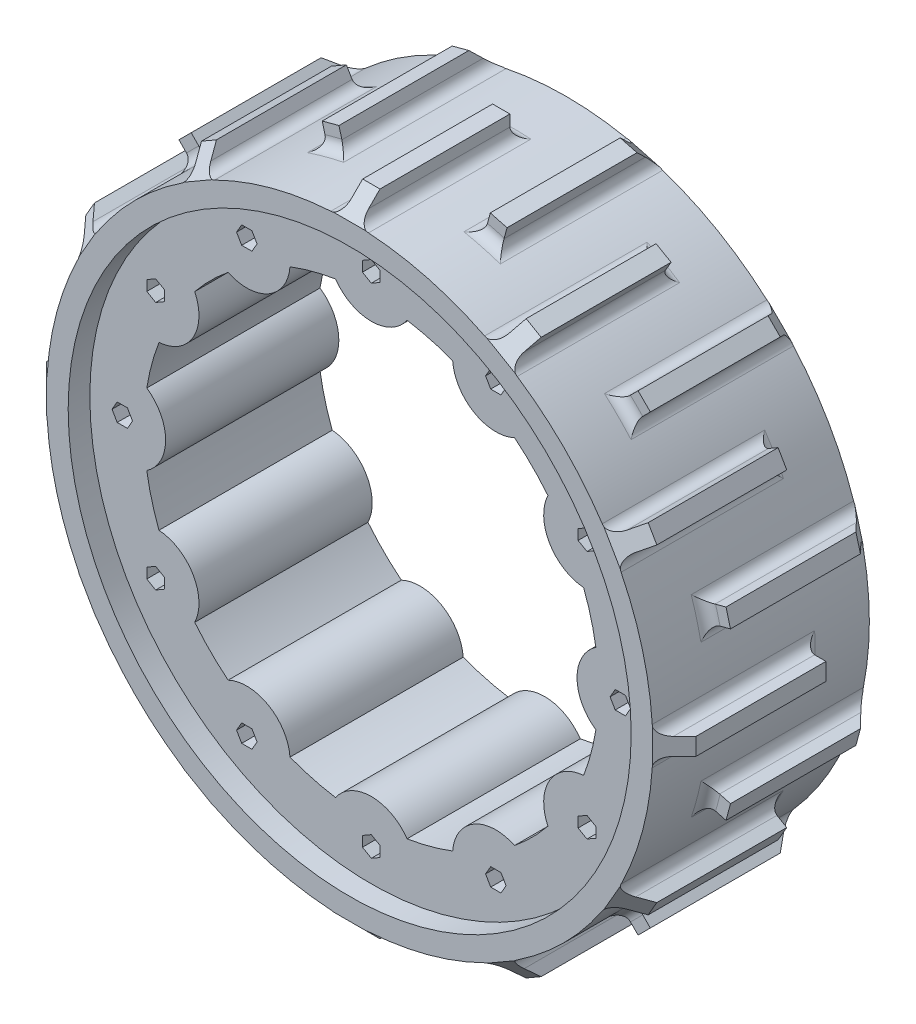
SolidWorks part; units mm, degrees
material "ABS"
ref_plane "前视基准面" through (0, 0, 0) normal (0, 0, 1) x (1, 0, 0)
ref_plane "上视基准面" through (0, 0, 0) normal (0, 1, 0) x (1, 0, 0)
ref_plane "右视基准面" through (0, 0, 0) normal (1, 0, 0) x (0, 0, -1)
other "Configuration Table"
sketch "草图1" plane through (0, 0, 0) normal (0, 0, 1) x (1, 0, 0)
  circle A0 centre (0, 0) radius 140
  dimension "D1" = 280
extrude "凸台-拉伸1" add sketch "草图1" along normal blind 100
sketch "草图2" plane through (0, 0, 100) normal (0, 0, 1) x (1, 0, 0)
  circle A0 centre (0, 0) radius 105
  dimension "D1" = 210
extrude "切除-拉伸1" cut sketch "草图2" against normal blind 100
sketch "草图3" plane through (0, 0, 100) normal (0, 0, 1) x (1, 0, 0)
  circle A0 centre (0, 0) radius 115 construction
  circle A1 centre (0, 115) radius 20
  circle A2 centre (57.5, 99.5929) radius 20
  circle A3 centre (99.5929, 57.5) radius 20
  circle A4 centre (115, 0) radius 20
  circle A5 centre (99.5929, -57.5) radius 20
  circle A6 centre (57.5, -99.5929) radius 20
  circle A7 centre (0, -115) radius 20
  circle A8 centre (-57.5, -99.5929) radius 20
  circle A9 centre (-99.5929, -57.5) radius 20
  circle A10 centre (-115, 0) radius 20
  circle A11 centre (-99.5929, 57.5) radius 20
  circle A12 centre (-57.5, 99.5929) radius 20
  point P30 (0, 0)
  dimension "D1" = 230
  dimension "D2" = 40
  dimension "D3" = 12
extrude "凸台-拉伸2" add sketch "草图3" against normal through all
sketch "草图4" plane through (0, 0, 100) normal (0, 0, 1) x (1, 0, 0)
  circle A0 centre (0, 0) radius 130
  dimension "D1" = 260
extrude "切除-拉伸2" cut sketch "草图4" against normal blind 10
sketch "草图5" plane through (0, 0, 0) normal (0, 0, -1) x (-1, 0, 0)
  circle A1 centre (0, 0) radius 130
  circle A2 centre (0, 0) radius 130
  dimension "D1" = 0
extrude "切除-拉伸3" cut sketch "草图5" against normal blind 10
sketch "草图6" plane through (0, 0, 90) normal (0, 0, 1) x (1, 0, 0)
  line L0 (55.1329, 95.4929) -> (59.8671, 95.4929)
  line L1 (0, 110.2657) -> (4.1, 112.6329)
  line L2 (4.1, 112.6329) -> (4.1, 117.3671)
  line L3 (4.1, 117.3671) -> (0, 119.7343)
  line L4 (0, 119.7343) -> (-4.1, 117.3671)
  line L5 (-4.1, 117.3671) -> (-4.1, 112.6329)
  line L6 (-4.1, 112.6329) -> (0, 110.2657)
  line L7 (59.8671, 95.4929) -> (62.2343, 99.5929)
  line L8 (62.2343, 99.5929) -> (59.8671, 103.6929)
  line L9 (59.8671, 103.6929) -> (55.1329, 103.6929)
  line L10 (55.1329, 103.6929) -> (52.7657, 99.5929)
  line L11 (52.7657, 99.5929) -> (55.1329, 95.4929)
  line L12 (95.4929, 55.1329) -> (99.5929, 52.7657)
  line L13 (99.5929, 52.7657) -> (103.6929, 55.1329)
  line L14 (103.6929, 55.1329) -> (103.6929, 59.8671)
  line L15 (103.6929, 59.8671) -> (99.5929, 62.2343)
  line L16 (99.5929, 62.2343) -> (95.4929, 59.8671)
  line L17 (95.4929, 59.8671) -> (95.4929, 55.1329)
  line L18 (110.2657, 0) -> (112.6329, -4.1)
  line L19 (112.6329, -4.1) -> (117.3671, -4.1)
  line L20 (117.3671, -4.1) -> (119.7343, 0)
  line L21 (119.7343, 0) -> (117.3671, 4.1)
  line L22 (117.3671, 4.1) -> (112.6329, 4.1)
  line L23 (112.6329, 4.1) -> (110.2657, 0)
  line L24 (95.4929, -55.1329) -> (95.4929, -59.8671)
  line L25 (95.4929, -59.8671) -> (99.5929, -62.2343)
  line L26 (99.5929, -62.2343) -> (103.6929, -59.8671)
  line L27 (103.6929, -59.8671) -> (103.6929, -55.1329)
  line L28 (103.6929, -55.1329) -> (99.5929, -52.7657)
  line L29 (99.5929, -52.7657) -> (95.4929, -55.1329)
  line L30 (55.1329, -95.4929) -> (52.7657, -99.5929)
  line L31 (52.7657, -99.5929) -> (55.1329, -103.6929)
  line L32 (55.1329, -103.6929) -> (59.8671, -103.6929)
  line L33 (59.8671, -103.6929) -> (62.2343, -99.5929)
  line L34 (62.2343, -99.5929) -> (59.8671, -95.4929)
  line L35 (59.8671, -95.4929) -> (55.1329, -95.4929)
  line L36 (0, -110.2657) -> (-4.1, -112.6329)
  line L37 (-4.1, -112.6329) -> (-4.1, -117.3671)
  line L38 (-4.1, -117.3671) -> (0, -119.7343)
  line L39 (0, -119.7343) -> (4.1, -117.3671)
  line L40 (4.1, -117.3671) -> (4.1, -112.6329)
  line L41 (4.1, -112.6329) -> (0, -110.2657)
  line L42 (-55.1329, -95.4929) -> (-59.8671, -95.4929)
  line L43 (-59.8671, -95.4929) -> (-62.2343, -99.5929)
  line L44 (-62.2343, -99.5929) -> (-59.8671, -103.6929)
  line L45 (-59.8671, -103.6929) -> (-55.1329, -103.6929)
  line L46 (-55.1329, -103.6929) -> (-52.7657, -99.5929)
  line L47 (-52.7657, -99.5929) -> (-55.1329, -95.4929)
  line L48 (-95.4929, -55.1329) -> (-99.5929, -52.7657)
  line L49 (-99.5929, -52.7657) -> (-103.6929, -55.1329)
  line L50 (-103.6929, -55.1329) -> (-103.6929, -59.8671)
  line L51 (-103.6929, -59.8671) -> (-99.5929, -62.2343)
  line L52 (-99.5929, -62.2343) -> (-95.4929, -59.8671)
  line L53 (-95.4929, -59.8671) -> (-95.4929, -55.1329)
  line L54 (-110.2657, 0) -> (-112.6329, 4.1)
  line L55 (-112.6329, 4.1) -> (-117.3671, 4.1)
  line L56 (-117.3671, 4.1) -> (-119.7343, 0)
  line L57 (-119.7343, 0) -> (-117.3671, -4.1)
  line L58 (-117.3671, -4.1) -> (-112.6329, -4.1)
  line L59 (-112.6329, -4.1) -> (-110.2657, 0)
  line L60 (-95.4929, 55.1329) -> (-95.4929, 59.8671)
  line L61 (-95.4929, 59.8671) -> (-99.5929, 62.2343)
  line L62 (-99.5929, 62.2343) -> (-103.6929, 59.8671)
  line L63 (-103.6929, 59.8671) -> (-103.6929, 55.1329)
  line L64 (-103.6929, 55.1329) -> (-99.5929, 52.7657)
  line L65 (-99.5929, 52.7657) -> (-95.4929, 55.1329)
  line L66 (-55.1329, 95.4929) -> (-52.7657, 99.5929)
  line L67 (-52.7657, 99.5929) -> (-55.1329, 103.6929)
  line L68 (-55.1329, 103.6929) -> (-59.8671, 103.6929)
  line L69 (-59.8671, 103.6929) -> (-62.2343, 99.5929)
  line L70 (-62.2343, 99.5929) -> (-59.8671, 95.4929)
  line L71 (-59.8671, 95.4929) -> (-55.1329, 95.4929)
  circle A0 centre (0, 115) radius 4.1 construction
  circle A1 centre (57.5, 99.5929) radius 4.1 construction
  circle A2 centre (99.5929, 57.5) radius 4.1 construction
  circle A3 centre (115, 0) radius 4.1 construction
  circle A4 centre (99.5929, -57.5) radius 4.1 construction
  circle A5 centre (57.5, -99.5929) radius 4.1 construction
  circle A6 centre (0, -115) radius 4.1 construction
  circle A7 centre (-57.5, -99.5929) radius 4.1 construction
  circle A8 centre (-99.5929, -57.5) radius 4.1 construction
  circle A9 centre (-115, 0) radius 4.1 construction
  circle A10 centre (-99.5929, 57.5) radius 4.1 construction
  circle A11 centre (-57.5, 99.5929) radius 4.1 construction
  point P100 (0, 0)
  dimension "D1" = 8.2
  dimension "D2" = 12
extrude "切除-拉伸4" cut sketch "草图6" against normal through all
sketch "草图7" plane through (0, 0, 100) normal (0, 0, 1) x (1, 0, 0)
  line L0 (0, 0) -> (0, 139.9428) construction
  line L1 (66.5073, 123.1941) -> (73.4355, 119.1941)
  line L2 (-4, 139.9428) -> (4, 139.9428)
  line L3 (-4, 139.9428) -> (-4, 149.9428)
  line L4 (-4, 149.9428) -> (4, 149.9428)
  line L5 (4, 139.9428) -> (4, 149.9428)
  line L6 (73.4355, 119.1941) -> (78.4355, 127.8543)
  line L7 (66.5073, 123.1941) -> (71.5073, 131.8543)
  line L8 (71.5073, 131.8543) -> (78.4355, 127.8543)
  line L9 (119.1941, 73.4355) -> (123.1941, 66.5073)
  line L10 (123.1941, 66.5073) -> (131.8543, 71.5073)
  line L11 (119.1941, 73.4355) -> (127.8543, 78.4355)
  line L12 (127.8543, 78.4355) -> (131.8543, 71.5073)
  line L13 (139.9428, 4) -> (139.9428, -4)
  line L14 (139.9428, -4) -> (149.9428, -4)
  line L15 (139.9428, 4) -> (149.9428, 4)
  line L16 (149.9428, 4) -> (149.9428, -4)
  line L17 (123.1941, -66.5073) -> (119.1941, -73.4355)
  line L18 (119.1941, -73.4355) -> (127.8543, -78.4355)
  line L19 (123.1941, -66.5073) -> (131.8543, -71.5073)
  line L20 (131.8543, -71.5073) -> (127.8543, -78.4355)
  line L21 (73.4355, -119.1941) -> (66.5073, -123.1941)
  line L22 (66.5073, -123.1941) -> (71.5073, -131.8543)
  line L23 (73.4355, -119.1941) -> (78.4355, -127.8543)
  line L24 (78.4355, -127.8543) -> (71.5073, -131.8543)
  line L25 (4, -139.9428) -> (-4, -139.9428)
  line L26 (-4, -139.9428) -> (-4, -149.9428)
  line L27 (4, -139.9428) -> (4, -149.9428)
  line L28 (4, -149.9428) -> (-4, -149.9428)
  line L29 (-66.5073, -123.1941) -> (-73.4355, -119.1941)
  line L30 (-73.4355, -119.1941) -> (-78.4355, -127.8543)
  line L31 (-66.5073, -123.1941) -> (-71.5073, -131.8543)
  line L32 (-71.5073, -131.8543) -> (-78.4355, -127.8543)
  line L33 (-119.1941, -73.4355) -> (-123.1941, -66.5073)
  line L34 (-123.1941, -66.5073) -> (-131.8543, -71.5073)
  line L35 (-119.1941, -73.4355) -> (-127.8543, -78.4355)
  line L36 (-127.8543, -78.4355) -> (-131.8543, -71.5073)
  line L37 (-139.9428, -4) -> (-139.9428, 4)
  line L38 (-139.9428, 4) -> (-149.9428, 4)
  line L39 (-139.9428, -4) -> (-149.9428, -4)
  line L40 (-149.9428, -4) -> (-149.9428, 4)
  line L41 (-123.1941, 66.5073) -> (-119.1941, 73.4355)
  line L42 (-119.1941, 73.4355) -> (-127.8543, 78.4355)
  line L43 (-123.1941, 66.5073) -> (-131.8543, 71.5073)
  line L44 (-131.8543, 71.5073) -> (-127.8543, 78.4355)
  line L45 (-73.4355, 119.1941) -> (-66.5073, 123.1941)
  line L46 (-66.5073, 123.1941) -> (-71.5073, 131.8543)
  line L47 (-73.4355, 119.1941) -> (-78.4355, 127.8543)
  line L48 (-78.4355, 127.8543) -> (-71.5073, 131.8543)
  circle A1 centre (0, 0) radius 140 construction
  point P57 (0, 0)
  dimension "D1" = 10
  dimension "D2" = 8
  dimension "D3" = 12
extrude "凸台-拉伸3" add sketch "草图7" against normal blind 70
sketch "草图9" plane through (0, 0, 0) normal (0, 0, -1) x (-1, 0, 0)
  line L0 (0, 0) -> (0, 140) construction
  line L1 (0, 0) -> (36.2199, 135.1744) construction
  line L2 (34.9444, 145.8689) -> (32.3562, 136.2097)
  line L3 (32.3562, 136.2097) -> (40.0836, 134.1391)
  line L4 (40.0836, 134.1391) -> (42.6718, 143.7984)
  line L5 (42.6718, 143.7984) -> (34.9444, 145.8689)
  line L6 (101.783, 96.1261) -> (108.854, 103.1972)
  line L7 (108.854, 103.1972) -> (103.1972, 108.854)
  line L8 (103.1972, 108.854) -> (96.1261, 101.783)
  line L9 (96.1261, 101.783) -> (101.783, 96.1261)
  line L10 (136.2097, 32.3562) -> (145.8689, 34.9444)
  line L11 (145.8689, 34.9444) -> (143.7984, 42.6718)
  line L12 (143.7984, 42.6718) -> (134.1391, 40.0836)
  line L13 (134.1391, 40.0836) -> (136.2097, 32.3562)
  line L14 (134.1391, -40.0836) -> (143.7984, -42.6718)
  line L15 (143.7984, -42.6718) -> (145.8689, -34.9444)
  line L16 (145.8689, -34.9444) -> (136.2097, -32.3562)
  line L17 (136.2097, -32.3562) -> (134.1391, -40.0836)
  line L18 (96.1261, -101.783) -> (103.1972, -108.854)
  line L19 (103.1972, -108.854) -> (108.854, -103.1972)
  line L20 (108.854, -103.1972) -> (101.783, -96.1261)
  line L21 (101.783, -96.1261) -> (96.1261, -101.783)
  line L22 (32.3562, -136.2097) -> (34.9444, -145.8689)
  line L23 (34.9444, -145.8689) -> (42.6718, -143.7984)
  line L24 (42.6718, -143.7984) -> (40.0836, -134.1391)
  line L25 (40.0836, -134.1391) -> (32.3562, -136.2097)
  line L26 (-40.0836, -134.1391) -> (-42.6718, -143.7984)
  line L27 (-42.6718, -143.7984) -> (-34.9444, -145.8689)
  line L28 (-34.9444, -145.8689) -> (-32.3562, -136.2097)
  line L29 (-32.3562, -136.2097) -> (-40.0836, -134.1391)
  line L30 (-101.783, -96.1261) -> (-108.854, -103.1972)
  line L31 (-108.854, -103.1972) -> (-103.1972, -108.854)
  line L32 (-103.1972, -108.854) -> (-96.1261, -101.783)
  line L33 (-96.1261, -101.783) -> (-101.783, -96.1261)
  line L34 (-136.2097, -32.3562) -> (-145.8689, -34.9444)
  line L35 (-145.8689, -34.9444) -> (-143.7984, -42.6718)
  line L36 (-143.7984, -42.6718) -> (-134.1391, -40.0836)
  line L37 (-134.1391, -40.0836) -> (-136.2097, -32.3562)
  line L38 (-134.1391, 40.0836) -> (-143.7984, 42.6718)
  line L39 (-143.7984, 42.6718) -> (-145.8689, 34.9444)
  line L40 (-145.8689, 34.9444) -> (-136.2097, 32.3562)
  line L41 (-136.2097, 32.3562) -> (-134.1391, 40.0836)
  line L42 (-96.1261, 101.783) -> (-103.1972, 108.854)
  line L43 (-103.1972, 108.854) -> (-108.854, 103.1972)
  line L44 (-108.854, 103.1972) -> (-101.783, 96.1261)
  line L45 (-101.783, 96.1261) -> (-96.1261, 101.783)
  line L46 (-32.3562, 136.2097) -> (-34.9444, 145.8689)
  line L47 (-34.9444, 145.8689) -> (-42.6718, 143.7984)
  line L48 (-42.6718, 143.7984) -> (-40.0836, 134.1391)
  line L49 (-40.0836, 134.1391) -> (-32.3562, 136.2097)
  arc A0 (4, 139.9428) -> (-4, 139.9428) centre (0, 0) ccw construction
  circle A2 centre (0, 0) radius 140 construction
  point P60 (0, 0)
  dimension "D1" = 15
  dimension "D2" = 8
  dimension "D3" = 10
  dimension "D4" = 12
extrude "凸台-拉伸4" add sketch "草图9" against normal blind 70
fillet "圆角3" radius 5 72 edges at (123.1941, -66.5073, 65) (121.2436, -70, 30) (119.1941, -73.4355, 65) (101.783, -96.1261, 35) (98.9949, -98.9949, 70) (73.4355, -119.1941, 65) (70, -121.2436, 30) (40.0836, -134.1391, 35) (36.2347, -135.2296, 70) (32.3562, -136.2097, 35) (66.5073, -123.1941, 65) (96.1261, -101.783, 35) (4, -139.9428, 65) (0, -140, 30) (-4, -139.9428, 65) (-32.3562, -136.2097, 35) (-36.2347, -135.2296, 70) (-40.0836, -134.1391, 35) (-66.5073, -123.1941, 65) (-70, -121.2436, 30) (-73.4355, -119.1941, 65) (-96.1261, -101.783, 35) (-98.9949, -98.9949, 70) (-101.783, -96.1261, 35) (-119.1941, -73.4355, 65) (-121.2436, -70, 30) (-123.1941, -66.5073, 65) (-134.1391, -40.0836, 35) (-135.2296, -36.2347, 70) (-136.2097, -32.3562, 35) (-139.9428, -4, 65) (-140, 0, 30) (-139.9428, 4, 65) (-136.2097, 32.3562, 35) (-135.2296, 36.2347, 70) (-134.1391, 40.0836, 35) (-123.1941, 66.5073, 65) (-121.2436, 70, 30) (-119.1941, 73.4355, 65) (-101.783, 96.1261, 35) (-98.9949, 98.9949, 70) (-96.1261, 101.783, 35) (-73.4355, 119.1941, 65) (-70, 121.2436, 30) (-66.5073, 123.1941, 65) (-40.0836, 134.1391, 35) (-36.2347, 135.2296, 70) (-32.3562, 136.2097, 35) (-4, 139.9428, 65) (0, 140, 30) (4, 139.9428, 65) (32.3562, 136.2097, 35) (36.2347, 135.2296, 70) (40.0836, 134.1391, 35) (66.5073, 123.1941, 65) (70, 121.2436, 30) (73.4355, 119.1941, 65) (119.1941, 73.4355, 65) (121.2436, 70, 30) (123.1941, 66.5073, 65) (139.9428, 4, 65) (140, 0, 30) (139.9428, -4, 65) (96.1261, 101.783, 35) (98.9949, 98.9949, 70) (101.783, 96.1261, 35) (134.1391, 40.0836, 35) (135.2296, 36.2347, 70) (136.2097, 32.3562, 35) (136.2097, -32.3562, 35) (135.2296, -36.2347, 70) (134.1391, -40.0836, 35)
chamfer "倒角1" distance 10 angle 45 24 edges at (74.9714, 129.8543, 100) (106.0256, 106.0256, 0) (129.8543, 74.9714, 100) (144.8337, 38.8081, 0) (149.9428, 0, 100) (144.8337, -38.8081, 0) (129.8543, -74.9714, 100) (106.0256, -106.0256, 0) (74.9714, -129.8543, 100) (38.8081, -144.8337, 0) (0, -149.9428, 100) (-38.8081, -144.8337, 0) (-74.9714, -129.8543, 100) (-106.0256, -106.0256, 0) (-129.8543, -74.9714, 100) (-144.8337, -38.8081, 0) (-149.9428, 0, 100) (-129.8543, 74.9714, 100) (-74.9714, 129.8543, 100) (0, 149.9428, 100) (-144.8337, 38.8081, 0) (-106.0256, 106.0256, 0) (-38.8081, 144.8337, 0) (38.8081, 144.8337, 0)
sketch "草图10" plane through (0, 0, 0) normal (0, 0, -1) x (-1, 0, 0)
  line L0 (0, 0) -> (25.9267, 162.9503)
  line L1 (0, 0) -> (-128.1557, 103.9284)
  line L2 (0, 0) -> (0, 165) construction
  arc A0 (-128.1557, 103.9284) -> (25.9267, 162.9503) centre (0, 0) ccw
  point P1 (0, 0)
  point P3 (0, 0)
  dimension "D1" = 330
  dimension "D3" = 60
extrude "切除-拉伸6" [suppressed] cut sketch "草图10" against normal through all
fillet "圆角4" [suppressed] radius 10
